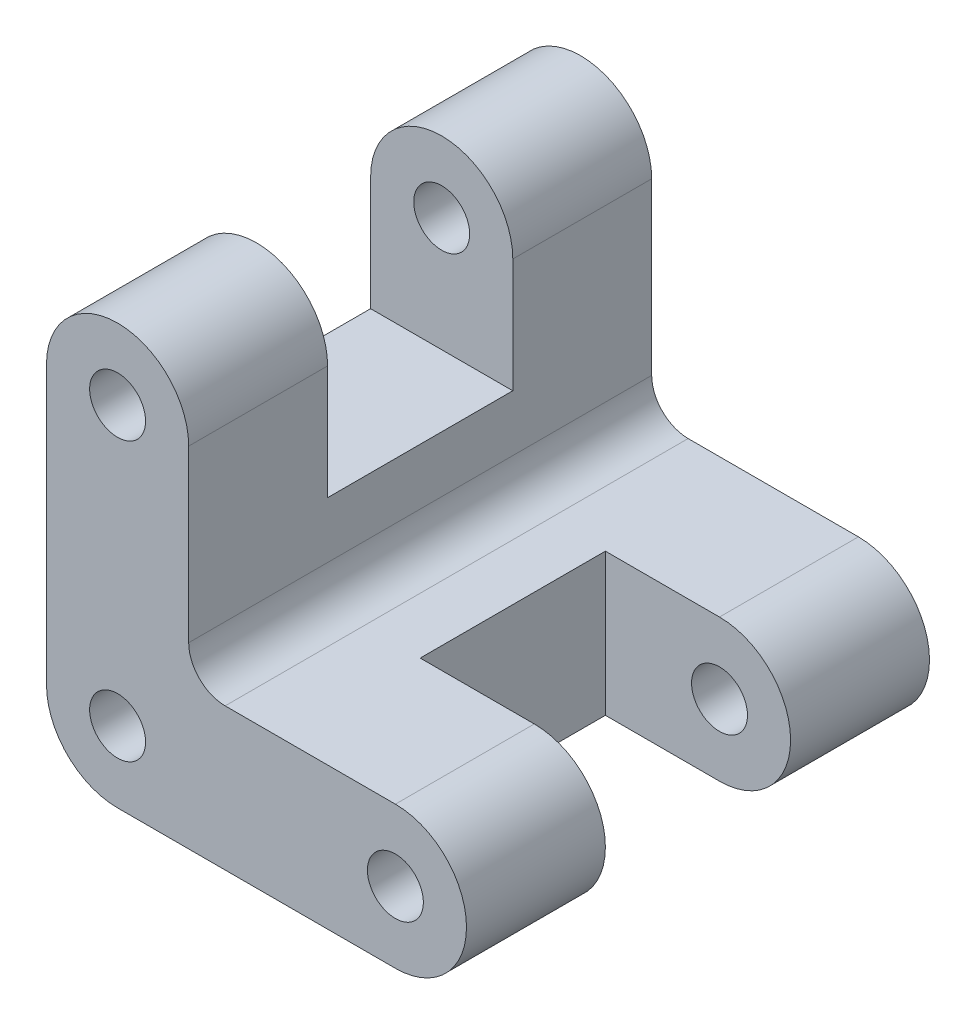
SolidWorks part; units mm, degrees
ref_plane "Front Plane" through (0, 0, 0) normal (0, 0, 1) x (1, 0, 0)
ref_plane "Top Plane" through (0, 0, 0) normal (0, 1, 0) x (1, 0, 0)
ref_plane "Right Plane" through (0, 0, 0) normal (1, 0, 0) x (0, 0, -1)
sketch "Sketch1" plane through (0, 0, 0) normal (0, 0, 1) x (1, 0, 0)
  line L0 (0, 0) -> (0, 156.1567) construction
  line L1 (0, 0) -> (161.2153, 0) construction
  line L2 (-19.5, 76.2) -> (-19.5, 0)
  line L3 (0, -19.5) -> (76.2, -19.5)
  line L4 (-19.5, 76.2) -> (82.486, 76.2) construction
  line L5 (19.5, 76.2) -> (19.5, 19.5)
  line L8 (19.5, 19.5) -> (76.2, 19.5)
  circle A0 centre (0, 0) radius 7.67
  circle A1 centre (0, 76.2) radius 7.67
  circle A2 centre (76.2, 0) radius 7.67
  arc A3 (-19.5, 76.2) -> (19.5, 76.2) centre (0, 76.2) cw
  arc A4 (76.2, -19.5) -> (76.2, 19.5) centre (76.2, 0) ccw
  arc A5 (-19.5, 0) -> (0, -19.5) centre (0, 0) ccw
  point P13 (19.5, 76.2)
  point P21 (0, 95.7)
  dimension "D7" = 15.34
  dimension "D2" = 19.5
  dimension "D3" = 115.2
  dimension "D4" = 19.5
  dimension "D5" = 19.5
  dimension "D10" = 19.5
  dimension "D11" = 19.5
extrude "Boss-Extrude1" add sketch "Sketch1" along normal blind 127
fillet "Fillet1" radius 10 1 edges at (19.5, 19.5, 63.5)
sketch "Sketch2" plane through (0, 0, 0) normal (1, 0, 0) x (0, 0, -1)
  line L0 (0, 96.6112) -> (0, -96.6112) construction
  line L1 (-38.1, 115.6452) -> (-88.9, 115.6452)
  line L2 (-38.1, 115.6452) -> (-38.1, 44.9)
  line L3 (-38.1, 44.9) -> (-88.9, 44.9)
  line L4 (-88.9, 115.6452) -> (-88.9, 44.9)
  line L5 (-127, 76.2) -> (-127, 0) construction
  line L6 (0, 95.7) -> (-127, 95.7) construction
  point P4 (-97.3794, 40.167)
  dimension "D1" = 38.1
  dimension "D2" = 38.1
  dimension "D3" = 50.8
extrude "Cut-Extrude1" cut sketch "Sketch2" against normal through all both and the other way through all
ref_axis "Axis1" through (0, 0, -6.35) along (0, 0, 1)
ref_plane "Plane1" through (0, 0, 0) normal (-0.7071, 0.7071, 0) x (0, 0, 1)
mirror "Mirror1" about plane through (0, 0, 0) normal (-0.7071, 0.7071, 0) of "Cut-Extrude1"
